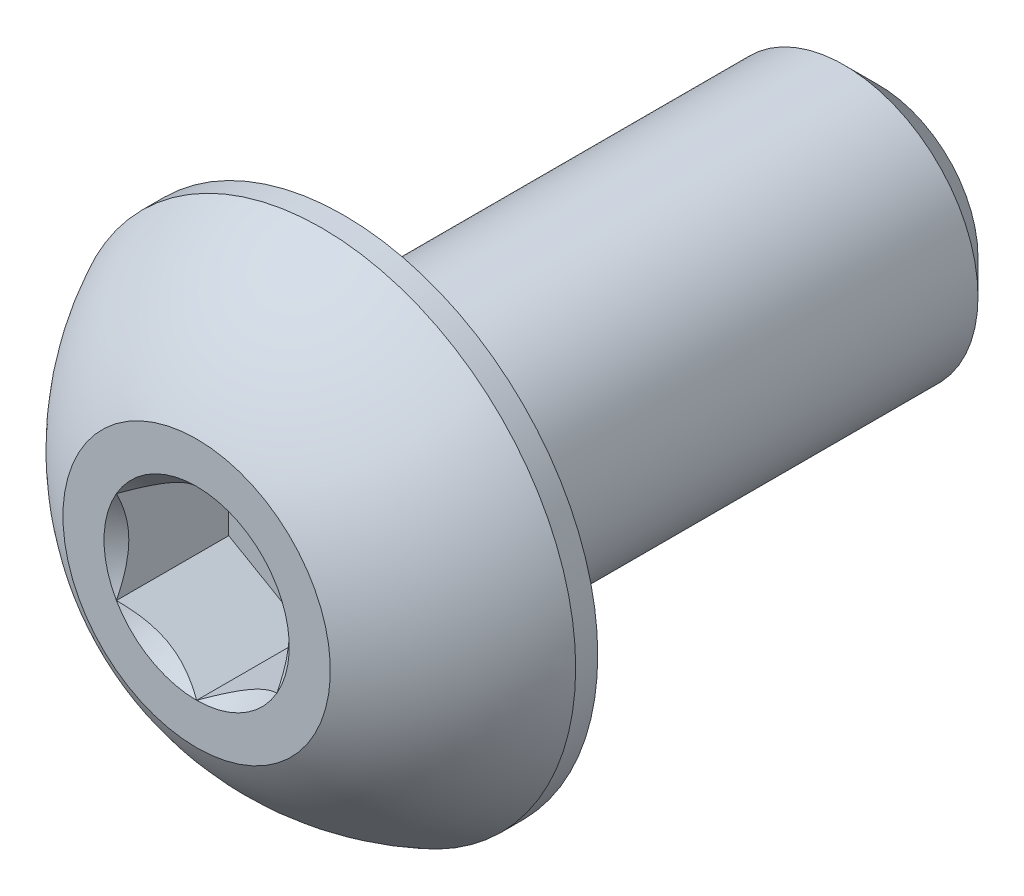
SolidWorks part; units mm, degrees
ref_plane "Front Plane" through (0, 0, 0) normal (0, 0, 1) x (1, 0, 0)
ref_plane "Top Plane" through (0, 0, 0) normal (0, 1, 0) x (1, 0, 0)
ref_plane "Right Plane" through (0, 0, 0) normal (1, 0, 0) x (0, 0, -1)
sketch "Sketch1" plane through (0, 0, 0) normal (1, 0, 0) x (0, 0, -1)
  line L0 (-6.375, 0) -> (6.375, 0) construction
  line L1 (-3.625, 4.75) -> (-3.625, -4.75) construction
  line L2 (6.375, 2.5) -> (6.375, -2.5) construction
  line L3 (6.325, 2.5866) -> (6.725, 1.8938) construction
  line L4 (6.725, 1.8938) -> (7.125, 2.5866) construction
  line L5 (7.125, 2.5866) -> (6.325, 2.5866) construction
  line L6 (6.375, 2.5) -> (7.075, 2.5) construction
  line L7 (6.725, 2.5866) -> (6.725, 2.5) construction
  line L8 (6.725, 2.5) -> (6.725, 1.9804) construction
  line L9 (6.725, 1.9804) -> (6.725, 1.8938) construction
  line L10 (6.675, 1.9804) -> (6.775, 1.9804)
  line L11 (6.35, 2.5433) -> (7.1, 2.5433)
  line L12 (6.775, 1.9804) -> (7.1, 2.5433)
  line L13 (6.675, 1.9804) -> (6.35, 2.5433)
  line L14 (-6.375, 1.5) -> (-6.375, -1.5) construction
  line L15 (6.375, 2.5) -> (-3.625, 2.5) construction
  point P3 (-3.625, 0)
  point P6 (-4.275, 0)
  point P21 (6.725, 2.5433)
  point P24 (-4.0375, 4.75)
  point P25 (4.375, -2.5)
  point P26 (-6.375, 2.5)
  dimension "Head Height" = 2.75
  dimension "Length" = 10
  dimension "Head Dia" = 9.5
  dimension "Thread Dia" = 5
  dimension "Pitch" = 0.8
  dimension "D2" = 0.1
  dimension "Drive Size" = 3
  dimension "D1" = 2.1
  dimension "D3" = 0.4125
  dimension "D4" = 2
sketch "Sketch2" plane through (0, 0, 0) normal (1, 0, 0) x (0, 0, -1)
  line L0 (-6.375, 0) -> (6.375, 0)
  line L1 (6.375, 0) -> (6.375, 1.86)
  line L2 (6.375, 2.5) -> (6.375, -2.5) construction
  line L3 (6.375, 1.86) -> (5.735, 2.5)
  line L4 (5.735, 2.5) -> (-3.625, 2.5)
  line L5 (-3.625, 4.75) -> (-3.625, -4.75) construction
  line L6 (-3.625, 2.5) -> (-3.625, 4.75)
  line L7 (-3.625, 4.75) -> (-4.0375, 4.75)
  line L8 (6.375, 2.5) -> (7.075, 2.5) construction
  line L9 (-6.375, 0) -> (-6.375, 2.5)
  arc A0 (-6.375, 2.5) -> (-4.0375, 4.75) centre (-1.7169, 0) cw
  dimension "D1" = 0.64
  dimension "D2" = 45
revolve "Revolve1" add sketch "Sketch2" angle 360 about L0
sketch "Sketch3" plane through (0, 0, 6.375) normal (0, 0, 1) x (1, 0, 0)
  line L1 (0, 1.7321) -> (-1.5, 0.866)
  line L2 (-1.5, 0.866) -> (-1.5, -0.866)
  line L3 (-1.5, -0.866) -> (0, -1.7321)
  line L4 (0, -1.7321) -> (1.5, -0.866)
  line L5 (1.5, -0.866) -> (1.5, 0.866)
  line L6 (1.5, 0.866) -> (0, 1.7321)
  circle A0 centre (0, 0) radius 1.5 construction
  dimension "D1" = 3
extrude "Cut-Extrude1" cut sketch "Sketch3" against normal up to vertex (2.1 mm away) up to point (0, 0, 4.275)
sketch "Sketch4" plane through (0, 0, 6.375) normal (0, 0, 1) x (1, 0, 0)
  circle A0 centre (0, 0) radius 1.7321
extrude "Cut-Extrude2" cut sketch "Sketch4" against normal blind 10 draft 45
split "Split1" [suppressed] bodies to split 106
sketch "Sketch5" [suppressed] plane through (0, 0, -6.375) normal (0, 0, -1) x (-1, 0, 0)
  circle A0 centre (0, 0) radius 2.5 construction
  circle A1 centre (0, 0) radius 2.5
curve "Helix/Spiral1" [suppressed] pitch 0.8 height 10.8 turns 13.5
sketch "Sketch6" [suppressed] plane through (0, 0, 0) normal (1, 0, 0) x (0, 0, -1)
  line L0 (6.675, 1.9804) -> (6.775, 1.9804) construction
  line L1 (6.675, 1.9804) -> (6.35, 2.5433) construction
  line L2 (6.35, 2.5433) -> (7.1, 2.5433) construction
  line L3 (6.775, 1.9804) -> (7.1, 2.5433) construction
  line L4 (6.675, 1.9804) -> (6.775, 1.9804)
  line L5 (6.675, 1.9804) -> (6.35, 2.5433)
  line L6 (6.35, 2.5433) -> (7.1, 2.5433)
  line L7 (6.775, 1.9804) -> (7.1, 2.5433)
sweep "Cut-Sweep1" [suppressed] cut profiles "Sketch6" path "Helix/Spiral1"
sketch "Sketch7" [suppressed] plane through (0, 0, 3.625) normal (0, 0, -1) x (-1, 0, 0)
  circle A1 centre (0, 0) radius 2.5
  circle A2 centre (0, 0) radius 2.5
  dimension "D1" = 0
extrude "Boss-Extrude1" [suppressed] add sketch "Sketch7" along normal blind 10 draft 30
equation "\"D2@Sketch1\" = \"Pitch@Sketch1\" / 8"
equation "\"D1@Sketch1\"=\"Drive Size@Sketch1\"*.7"
equation "\"D3@Sketch1\"=\"Head Height@Sketch1\"*.15"
equation "\"D1@Sketch2\"=\"Pitch@Sketch1\"*.8"
equation "\"D1@Sketch3\"=\"Drive Size@Sketch1\""
equation "\"D4@Helix/Spiral1\"=\"Pitch@Sketch1\""
equation "\"D3@Helix/Spiral1\"=\"Length@Sketch1\"+\"Pitch@Sketch1\""
equation "\"D4@Sketch1\"=\"Pitch@Sketch1\"*2.5"
